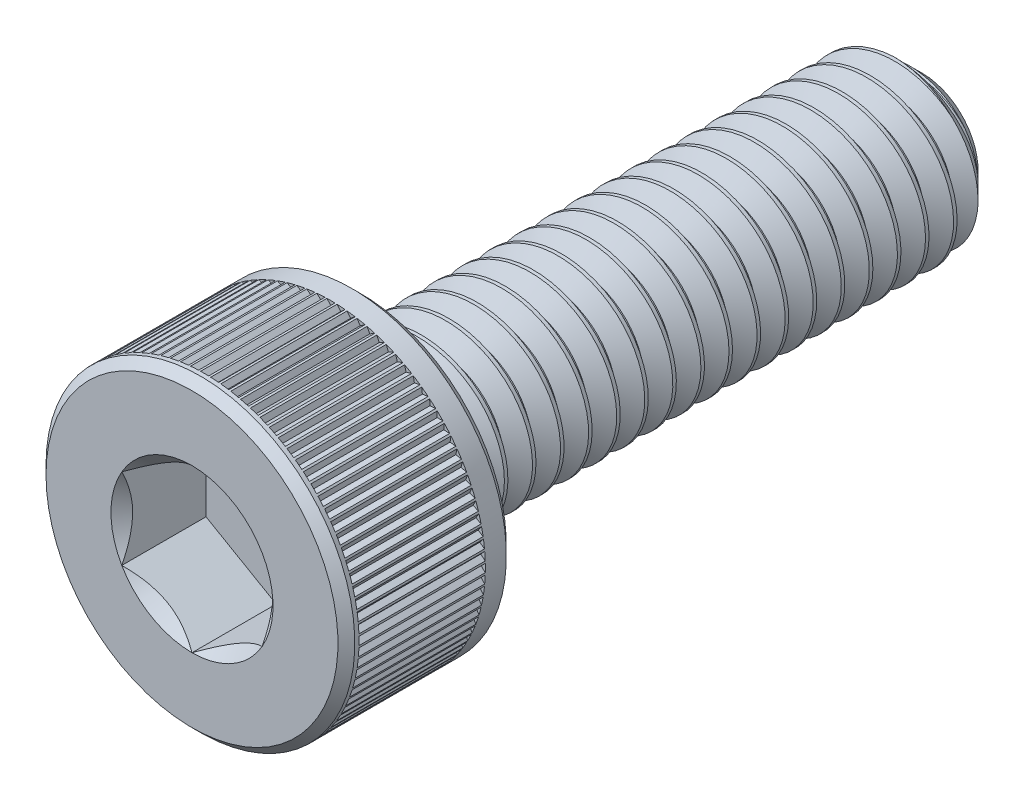
SolidWorks part; units mm, degrees
ref_plane "Front Plane" through (0, 0, 0) normal (0, 0, 1) x (1, 0, 0)
ref_plane "Top Plane" through (0, 0, 0) normal (0, 1, 0) x (1, 0, 0)
ref_plane "Right Plane" through (0, 0, 0) normal (1, 0, 0) x (0, 0, -1)
sketch "Sketch1" plane through (0, 0, 0) normal (1, 0, 0) x (0, 0, -1)
  line L0 (-6.5, 0) -> (6.5, 0) construction
  line L1 (6.5, 0) -> (6.5, 1) construction
  line L2 (6.5, 1) -> (6, 1.5) construction
  line L3 (6, 1.5) -> (-3.5, 1.5) construction
  line L5 (-3.5, 1.5) -> (-3.5, 2.75) construction
  line L6 (-3.5, 2.75) -> (-6.5, 2.75) construction
  line L7 (-6.5, 2.75) -> (-6.5, 0) construction
  line L8 (6.5, 1) -> (6.5, 1.5) construction
  line L9 (6.4688, 1.5541) -> (6.7188, 1.1211) construction
  line L10 (6.7188, 1.1211) -> (6.9688, 1.5541) construction
  line L11 (6.9688, 1.5541) -> (6.4688, 1.5541) construction
  line L12 (6.7188, 1.5541) -> (6.7188, 1.5) construction
  line L13 (6.7188, 1.1211) -> (6.7188, 1.1752) construction
  line L14 (6.6875, 1.1752) -> (6.75, 1.1752) construction
  line L15 (6.5, 1.5) -> (6.9375, 1.5) construction
  line L16 (6.4844, 1.5271) -> (6.9531, 1.5271) construction
  line L17 (6.5, 0) -> (6.5, -1.5) construction
  line L18 (-3.65, 2.75) -> (-3.5, 2.6) construction
  line L19 (-6.35, 2.75) -> (-6.5, 2.6) construction
  point P0 (-6.5, 1.25)
  point P3 (4.75, 1.5)
  point P4 (0, 0)
  point P22 (6.7188, 1.1752)
  point P24 (-3.5, 1.5)
  point P25 (6.7188, 1.5)
  point P28 (6.7188, 1.5271)
  point P29 (4.75, -1.5)
  point P31 (-5, 2.75)
  point P37 (-4.025, 2.75)
  point P38 (-6.275, 2.75)
  point P41 (-5, 0)
  dimension "head height" = 3
  dimension "D1" = 45
  dimension "Head Diameter" = 5.5
  dimension "Thread Size" = 3
  dimension "drive size" = 2.5
  dimension "Thread Pitch" = 0.5
  dimension "D2" = 0.0625
  dimension "D3" = 0.5
  dimension "D4" = 1.75
  dimension "D7" = 0.15
  dimension "D8" = 0.15
  dimension "D9" = 0.15
  dimension "D10" = 0.075
  dimension "D11" = 0.375
  dimension "length" = 10
  dimension "Drive Depth" = 1.5
sketch "Sketch2" plane through (0, 0, 0) normal (1, 0, 0) x (0, 0, -1)
  line L1 (-6.35, 2.75) -> (-3.65, 2.75)
  line L4 (6, 1.5) -> (6.5, 1)
  line L5 (6.5, 1) -> (6.5, 0)
  line L6 (-3.65, 2.75) -> (-3.5, 2.6) construction
  line L7 (6.5, 0) -> (-6.5, 0)
  line L8 (-6.35, 2.75) -> (-6.5, 2.6) construction
  line L9 (-3.65, 2.75) -> (-3.5, 2.6)
  line L10 (-6.35, 2.75) -> (-6.5, 2.6)
  line L11 (-6.5, 2.6) -> (-6.5, 0)
  line L12 (-3.5, 2.6) -> (-3.5, 1.5)
  line L13 (-3.5, 1.5) -> (6, 1.5)
revolve "Revolve1" add sketch "Sketch2" angle 360 about L7
sketch "Sketch3" plane through (0, 0, 6.5) normal (0, 0, 1) x (1, 0, 0)
  line L1 (0, 1.4434) -> (-1.25, 0.7217)
  line L2 (-1.25, 0.7217) -> (-1.25, -0.7217)
  line L3 (-1.25, -0.7217) -> (0, -1.4434)
  line L4 (0, -1.4434) -> (1.25, -0.7217)
  line L5 (1.25, -0.7217) -> (1.25, 0.7217)
  line L6 (1.25, 0.7217) -> (0, 1.4434)
  circle A0 centre (0, 0) radius 1.25 construction
  dimension "D1" = 2.5
extrude "Cut-Extrude1" cut sketch "Sketch3" against normal up to vertex (1.5 mm away) up to point (0, 0, 5)
sketch "Sketch4" plane through (0, 0, 6.5) normal (0, 0, 1) x (1, 0, 0)
  circle A0 centre (0, 0) radius 1.4434
extrude "Cut-Extrude2" cut sketch "Sketch4" against normal blind 0.5 draft 45
ref_plane "Plane1" through (0, 0, 3.5) normal (0, 0, 1) x (1, 0, 0)
split "Split1" bodies to split 106 resulting bodies 108 115 split by face at (-2.6, 0, 3.5)
sketch "Sketch6" plane through (0, 0, -6.5) normal (0, 0, -1) x (-1, 0, 0)
  circle A0 centre (0, 0) radius 1.5
curve "Helix/Spiral1" pitch 0.5 height 10.5 radius 1.5 centre (0, 0, -6.5) axis (0, 0, 1) start towards (0, 1, 0)
sketch "Sketch7" plane through (0, 0, 0) normal (1, 0, 0) x (0, 0, -1)
  line L0 (6.4844, 1.5271) -> (6.9531, 1.5271)
  line L1 (6.9531, 1.5271) -> (6.75, 1.1752)
  line L2 (6.75, 1.1752) -> (6.6875, 1.1752)
  line L3 (6.6875, 1.1752) -> (6.4844, 1.5271)
sweep "Cut-Sweep1" cut profiles "Sketch7" path "Helix/Spiral1" align with end faces yes
sketch "Sketch8" plane through (0, 0, 3.5) normal (0, 0, -1) x (-1, 0, 0)
  circle A0 centre (0, 0) radius 1.5
extrude "Boss-Extrude1" add sketch "Sketch8" along normal through all draft 45
ref_plane "Plane2" through (0, 0, 5) normal (0, 0, 1) x (1, 0, 0)
sketch "Sketch9" plane through (0, 0, 5) normal (0, 0, 1) x (1, 0, 0)
  line L0 (0, 2.6744) -> (0.072, 2.7491)
  line L1 (0, 2.6744) -> (-0.072, 2.7491)
  line L2 (0, 2.75) -> (0, 0) construction
  line L3 (-0.072, 2.7491) -> (0, 0) construction
  line L4 (0, 0) -> (0.072, 2.7491) construction
  arc A0 (0.072, 2.7491) -> (-0.072, 2.7491) centre (0, 0) ccw
  circle A1 centre (0, 0) radius 2.6744 construction
  dimension "D1" = 5.5
  dimension "D2" = 5.3487
  dimension "D3" = 3
extrude "Cut-Extrude4" cut sketch "Sketch9" against normal up to vertex (0.975 mm away) and the other way up to vertex (1.275 mm away) up to point (0, 2.75, 4.025) other way up to point (0, 2.75, 6.275)
pattern_circular "CirPattern2" count 96 over 360 about axis through (0, 0, 6.5) along (0, 0, -1) of "Cut-Extrude4"
equation "\"D2@Sketch1\" = \"Thread Pitch@Sketch1\" / 8"
equation "\"D3@Sketch1\" = \"Thread Pitch@Sketch1\""
equation "\"D3@Helix/Spiral1\" = \"length@Sketch1\" + \"Thread Pitch@Sketch1\""
equation "\"D4@Helix/Spiral1\" = \"Thread Pitch@Sketch1\""
equation "\"D4@Sketch1\" = \"Thread Pitch@Sketch1\" * 3.5"
equation "\"D7@Sketch1\"=\"head height@Sketch1\"*.05"
equation "\"D8@Sketch1\"=\"D7@Sketch1\""
equation "\"D9@Sketch1\"=\"D7@Sketch1\""
equation "\"D10@Sketch1\"=\"D7@Sketch1\"/2"
equation "\"D11@Sketch1\"=\"D10@Sketch1\"*5"
equation "\"D1@CirPattern2\"=( 360 / \"D3@Sketch9\" )*0.8"
equation "\"D1@Sketch3\" = \"drive size@Sketch1\""
equation "\"D2@Sketch9\"=\"Head Diameter@Sketch1\" * 0.9725"
